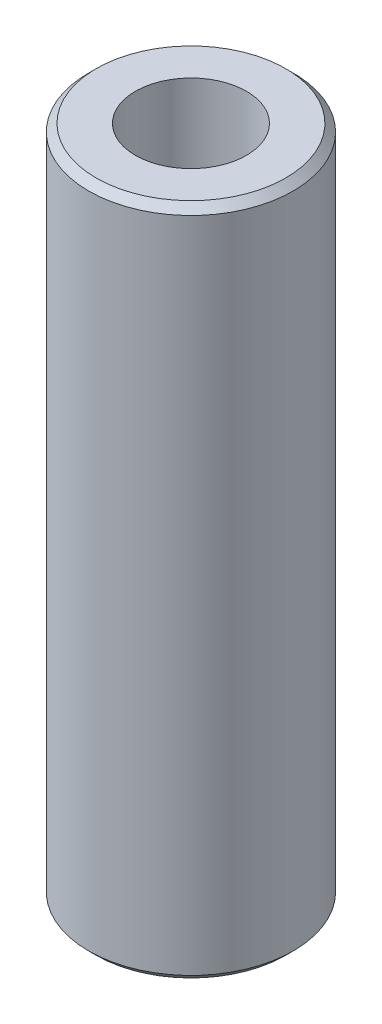
SolidWorks part; units mm, degrees
ref_plane "Front Plane" through (0, 0, 0) normal (0, 0, 1) x (1, 0, 0)
ref_plane "Top Plane" through (0, 0, 0) normal (0, 1, 0) x (1, 0, 0)
ref_plane "Right Plane" through (0, 0, 0) normal (1, 0, 0) x (0, 0, -1)
sketch "Sketch1" plane through (0, 0, 0) normal (0, 1, 0) x (1, 0, 0)
  circle A0 centre (0, 0) radius 60
  dimension "SHAFT_OD" = 120
extrude "Boss-Extrude1" add sketch "Sketch1" along normal blind 394.8801
sketch "Sketch2" plane through (0, 0, 0) normal (0, 1, 0) x (1, 0, 0)
  circle A0 centre (0, 0) radius 32.5808
  dimension "BORE_D" = 65.1616
extrude "Cut-Extrude1" cut sketch "Sketch2" along normal through all
chamfer "Chamfer1" distance 4.412 angle 45 2 edges at (0, 394.8801, 60) (0, 0, 60)
